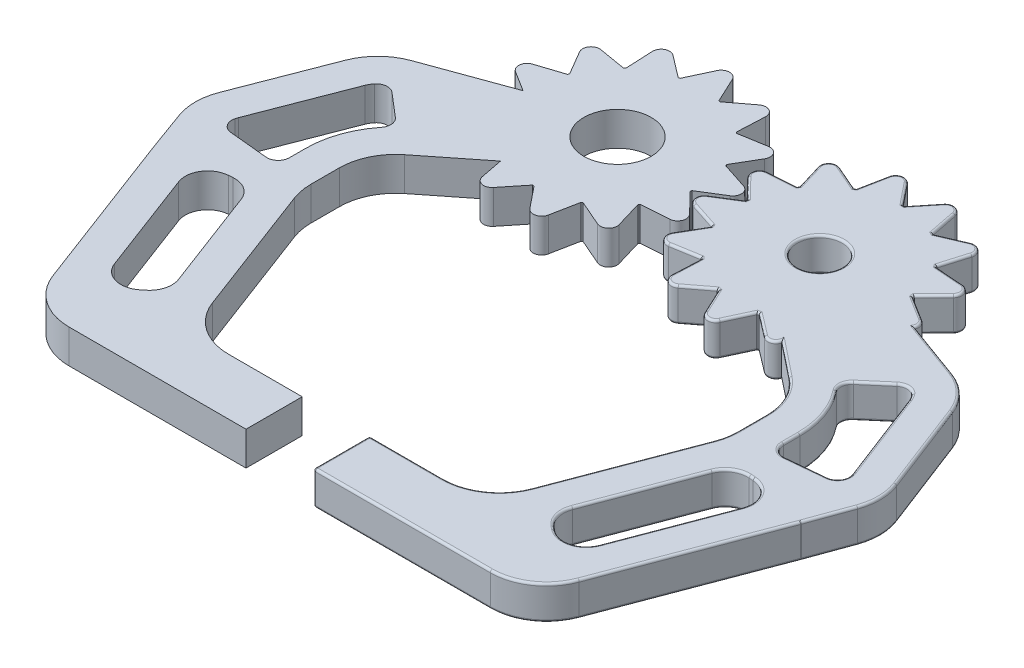
SolidWorks part; units mm, degrees
ref_plane "Front Plane" through (0, 0, 0) normal (0, 0, 1) x (1, 0, 0)
ref_plane "Top Plane" through (0, 0, 0) normal (0, 1, 0) x (1, 0, 0)
ref_plane "Right Plane" through (0, 0, 0) normal (1, 0, 0) x (0, 0, -1)
sketch "Sketch1" plane through (0, 0, 0) normal (0, 1, 0) x (1, 0, 0)
  line L0 (-9, 0) -> (-9, 13.9015) construction
  line L1 (-8.3203, 9.5423) -> (-7.2741, 7.2987)
  line L2 (-9.6797, 9.5423) -> (-10.7259, 7.2987)
  line L3 (-3.9636, 8.1334) -> (-4.0799, 5.6606)
  line L4 (-5.1673, 8.7652) -> (-7.1364, 7.2648)
  line L5 (-0.7607, 4.8612) -> (-2.0128, 2.7257)
  line L6 (-1.533, 5.9801) -> (-3.9737, 5.5666)
  line L7 (0.5547, 0.4754) -> (-1.5465, -0.8336)
  line L8 (0.3908, 1.825) -> (-1.9625, 2.5931)
  line L9 (-0.3188, -4.0193) -> (-2.7876, -4.2019)
  line L10 (0.1633, -2.7482) -> (-1.5636, -0.9744)
  line L11 (-3.1811, -7.5933) -> (-5.4519, -6.6077)
  line L12 (-2.1635, -6.6918) -> (-2.8682, -4.3187)
  line L13 (-7.3764, -9.4277) -> (-8.9291, -7.4997)
  line L14 (-6.0564, -9.1024) -> (-5.5775, -6.6736)
  line L15 (-11.9436, -9.1024) -> (-12.4225, -6.6736)
  line L16 (-10.6236, -9.4277) -> (-9.0709, -7.4997)
  line L17 (-15.8365, -6.6918) -> (-15.1318, -4.3187)
  line L18 (-14.8189, -7.5933) -> (-12.5481, -6.6077)
  line L19 (-18.1633, -2.7482) -> (-16.4364, -0.9744)
  line L20 (-17.6812, -4.0193) -> (-15.2124, -4.2019)
  line L21 (-18.3908, 1.825) -> (-16.0375, 2.5931)
  line L22 (-18.5547, 0.4754) -> (-16.4535, -0.8336)
  line L23 (-16.467, 5.9801) -> (-14.0263, 5.5666)
  line L24 (-17.2393, 4.8612) -> (-15.9872, 2.7257)
  line L25 (-12.8327, 8.7652) -> (-10.8636, 7.2648)
  line L26 (-14.0364, 8.1334) -> (-13.9201, 5.6606)
  circle A0 centre (-9, 0) radius 10 construction
  circle A1 centre (9, 0) radius 10 construction
  arc A2 (-7.1364, 7.2648) -> (-7.2741, 7.2987) centre (-9, 0) ccw
  arc A3 (-8.3203, 9.5423) -> (-9.6797, 9.5423) centre (-9, 9.2253) ccw
  arc A4 (-3.9636, 8.1334) -> (-5.1673, 8.7652) centre (-4.7128, 8.1686) ccw
  arc A5 (-0.7607, 4.8612) -> (-1.533, 5.9801) centre (-1.4077, 5.2406) ccw
  arc A6 (0.5547, 0.4754) -> (0.3908, 1.825) centre (0.1581, 1.112) ccw
  arc A7 (-0.3188, -4.0193) -> (0.1633, -2.7482) centre (-0.3741, -3.2714) ccw
  arc A8 (-3.1811, -7.5933) -> (-2.1635, -6.6918) centre (-2.8825, -6.9053) ccw
  arc A9 (-7.3764, -9.4277) -> (-6.0564, -9.1024) centre (-6.7922, -8.9573) ccw
  arc A10 (-11.9436, -9.1024) -> (-10.6236, -9.4277) centre (-11.2078, -8.9573) ccw
  arc A11 (-15.8365, -6.6918) -> (-14.8189, -7.5933) centre (-15.1175, -6.9053) ccw
  arc A12 (-18.1633, -2.7482) -> (-17.6812, -4.0193) centre (-17.6259, -3.2714) ccw
  arc A13 (-18.3908, 1.825) -> (-18.5547, 0.4754) centre (-18.1581, 1.112) ccw
  arc A14 (-16.467, 5.9801) -> (-17.2393, 4.8612) centre (-16.5923, 5.2406) ccw
  arc A15 (-12.8327, 8.7652) -> (-14.0364, 8.1334) centre (-13.2872, 8.1686) ccw
  arc A16 (-10.7259, 7.2987) -> (-10.8636, 7.2648) centre (-9, 0) ccw
  arc A17 (-13.9201, 5.6606) -> (-14.0263, 5.5666) centre (-9, 0) ccw
  arc A18 (-15.9872, 2.7257) -> (-16.0375, 2.5931) centre (-9, 0) ccw
  arc A19 (-16.4535, -0.8336) -> (-16.4364, -0.9744) centre (-9, 0) ccw
  arc A20 (-15.2124, -4.2019) -> (-15.1318, -4.3187) centre (-9, 0) ccw
  arc A21 (-12.5481, -6.6077) -> (-12.4225, -6.6736) centre (-9, 0) ccw
  arc A22 (-9.0709, -7.4997) -> (-8.9291, -7.4997) centre (-9, 0) ccw
  arc A23 (-5.5775, -6.6736) -> (-5.4519, -6.6077) centre (-9, 0) ccw
  arc A24 (-2.8682, -4.3187) -> (-2.7876, -4.2019) centre (-9, 0) ccw
  arc A25 (-1.5636, -0.9744) -> (-1.5465, -0.8336) centre (-9, 0) ccw
  arc A26 (-1.9625, 2.5931) -> (-2.0128, 2.7257) centre (-9, 0) ccw
  arc A27 (-3.9737, 5.5666) -> (-4.0799, 5.6606) centre (-9, 0) ccw
  point P15 (-9, 11)
  point P75 (-9, 0)
  dimension "D1" = 20
  dimension "D2" = 20
  dimension "D5" = 15
  dimension "D8" = 0.75
  dimension "D3" = 18
  dimension "D4" = 9
  dimension "D6" = 25
  dimension "D7" = 11
  dimension "D9" = 13
extrude "Boss-Extrude1" add sketch "Sketch1" along normal blind 3
sketch "Sketch2" plane through (0, 0, 0) normal (0, 1, 0) x (1, 0, 0)
  line L0 (9, 0) -> (12.5984, 14.6004) construction
  line L1 (11.9434, 9.1024) -> (12.4223, 6.6736)
  line L2 (10.6235, 9.4277) -> (9.0708, 7.4997)
  line L3 (15.8364, 6.6919) -> (15.1317, 4.3188)
  line L4 (14.8188, 7.5934) -> (12.5479, 6.6077)
  line L5 (18.1632, 2.7484) -> (16.4364, 0.9745)
  line L6 (17.6811, 4.0195) -> (15.2123, 4.2021)
  line L7 (18.3908, -1.8248) -> (16.0375, -2.593)
  line L8 (18.5547, -0.4752) -> (16.4535, 0.8337)
  line L9 (16.4672, -5.9799) -> (14.0264, -5.5665)
  line L10 (17.2394, -4.8611) -> (15.9872, -2.7256)
  line L11 (12.8328, -8.7651) -> (10.8638, -7.2647)
  line L12 (14.0366, -8.1333) -> (13.9202, -5.6605)
  line L13 (8.3205, -9.5423) -> (7.2742, -7.2987)
  line L14 (9.6799, -9.5423) -> (10.7261, -7.2987)
  line L15 (3.9638, -8.1335) -> (4.08, -5.6607)
  line L16 (5.1675, -8.7653) -> (7.1365, -7.2648)
  line L17 (0.7608, -4.8614) -> (2.0129, -2.7259)
  line L18 (1.5331, -5.9802) -> (3.9738, -5.5667)
  line L19 (-0.5547, -0.4756) -> (1.5465, 0.8334)
  line L20 (-0.3908, -1.8252) -> (1.9626, -2.5933)
  line L21 (0.3187, 4.0191) -> (2.7875, 4.2018)
  line L22 (-0.1633, 2.748) -> (1.5635, 0.9742)
  line L23 (3.1809, 7.5932) -> (5.4518, 6.6076)
  line L24 (2.1634, 6.6916) -> (2.8681, 4.3185)
  line L25 (7.3762, 9.4277) -> (8.9289, 7.4997)
  line L26 (6.0562, 9.1023) -> (5.5774, 6.6735)
  line L27 (9, 0) -> (9, 20.9978) construction
  arc A0 (5.5774, 6.6735) -> (5.4518, 6.6076) centre (9, 0) ccw
  arc A1 (11.9434, 9.1024) -> (10.6235, 9.4277) centre (11.2076, 8.9573) ccw
  arc A2 (15.8364, 6.6919) -> (14.8188, 7.5934) centre (15.1174, 6.9054) ccw
  arc A3 (18.1632, 2.7484) -> (17.6811, 4.0195) centre (17.6258, 3.2715) ccw
  arc A4 (18.3908, -1.8248) -> (18.5547, -0.4752) centre (18.1581, -1.1118) ccw
  arc A5 (16.4672, -5.9799) -> (17.2394, -4.8611) centre (16.5924, -5.2404) ccw
  arc A6 (12.8328, -8.7651) -> (14.0366, -8.1333) centre (13.2874, -8.1686) ccw
  arc A7 (8.3205, -9.5423) -> (9.6799, -9.5423) centre (9.0002, -9.2253) ccw
  arc A8 (3.9638, -8.1335) -> (5.1675, -8.7653) centre (4.7129, -8.1687) ccw
  arc A9 (0.7608, -4.8614) -> (1.5331, -5.9802) centre (1.4078, -5.2407) ccw
  arc A10 (-0.5547, -0.4756) -> (-0.3908, -1.8252) centre (-0.1581, -1.1122) ccw
  arc A11 (0.3187, 4.0191) -> (-0.1633, 2.748) centre (0.3741, 3.2712) ccw
  arc A12 (3.1809, 7.5932) -> (2.1634, 6.6916) centre (2.8823, 6.9051) ccw
  arc A13 (7.3762, 9.4277) -> (6.0562, 9.1023) centre (6.792, 8.9572) ccw
  arc A14 (2.8681, 4.3185) -> (2.7875, 4.2018) centre (9, 0) ccw
  arc A15 (1.5635, 0.9742) -> (1.5465, 0.8334) centre (9, 0) ccw
  arc A16 (1.9626, -2.5933) -> (2.0129, -2.7259) centre (9, 0) ccw
  arc A17 (3.9738, -5.5667) -> (4.08, -5.6607) centre (9, 0) ccw
  arc A18 (7.1365, -7.2648) -> (7.2742, -7.2987) centre (9, 0) ccw
  arc A19 (10.7261, -7.2987) -> (10.8638, -7.2647) centre (9, 0) ccw
  arc A20 (13.9202, -5.6605) -> (14.0264, -5.5665) centre (9, 0) ccw
  arc A21 (15.9872, -2.7256) -> (16.0375, -2.593) centre (9, 0) ccw
  arc A22 (16.4535, 0.8337) -> (16.4364, 0.9745) centre (9, 0) ccw
  arc A23 (15.2123, 4.2021) -> (15.1317, 4.3188) centre (9, 0) ccw
  arc A24 (12.5479, 6.6077) -> (12.4223, 6.6736) centre (9, 0) ccw
  arc A25 (9.0708, 7.4997) -> (8.9289, 7.4997) centre (9, 0) ccw
  point P11 (11.6323, 10.6804)
  point P73 (9, 0)
  dimension "D1" = 15
  dimension "D2" = 25
  dimension "D4" = 0.75
  dimension "D3" = 11
  dimension "D6" = 13.845
  dimension "D5" = 13
extrude "Boss-Extrude2" add sketch "Sketch2" along normal blind 3 separate body
sketch "Sketch3" plane through (0, 3, 0) normal (0, 1, 0) x (1, 0, 0)
  circle A0 centre (-9, 0) radius 3
  dimension "D1" = 6
extrude "Cut-Extrude1" cut sketch "Sketch3" against normal blind 3
sketch "Sketch4" plane through (0, 3, 0) normal (0, 1, 0) x (1, 0, 0)
  line L0 (-12, 0) -> (-15, 0)
  line L1 (-15, 0) -> (-24.0634, -3.2988)
  line L2 (-30.1807, -17.8135) -> (-28.8453, -21.4827)
  line L3 (-18.7439, -39.0643) -> (-3, -39.0643)
  line L4 (-12, -5.2004) -> (-11.2334, -6.1968)
  line L5 (-11.2334, -6.1968) -> (-17.0992, -10.8467)
  line L6 (-18.9932, -14.765) -> (-18.9932, -17.308)
  line L7 (-18.6701, -19.0761) -> (-14.2257, -30.8324)
  line L8 (-3, -34.0643) -> (-3, -39.0643)
  line L9 (-12, 0) -> (-12, -5.2004)
  line L10 (-9.5488, -34.0643) -> (-3, -34.0643)
  line L11 (-27.0179, -6.1968) -> (-30.1468, -14.3029)
  line L12 (-23.4209, -35.8324) -> (-28.8237, -21.5407)
  line L13 (0, 0) -> (0, 23.1588) construction
  line L14 (23.4209, -35.8324) -> (28.8237, -21.5407)
  line L15 (27.0179, -6.1968) -> (30.1468, -14.3029)
  line L16 (9.5488, -34.0643) -> (3, -34.0643)
  line L17 (12, 0) -> (12, -5.2004)
  line L18 (3, -34.0643) -> (3, -39.0643)
  line L19 (18.6701, -19.0761) -> (14.2257, -30.8324)
  line L20 (18.9932, -14.765) -> (18.9932, -17.308)
  line L21 (11.2334, -6.1968) -> (17.0992, -10.8467)
  line L22 (12, -5.2004) -> (11.2334, -6.1968)
  line L23 (18.7439, -39.0643) -> (3, -39.0643)
  line L24 (30.1807, -17.8135) -> (28.8453, -21.4827)
  line L25 (15, 0) -> (24.0634, -3.2988)
  line L26 (12, 0) -> (15, 0)
  line L27 (-24.2191, -7.2771) -> (-27.3481, -15.3832)
  line L28 (-21.9932, -14.765) -> (-21.9932, -17.308) construction
  line L29 (-21.9932, -14.765) -> (-21.9932, -16.2063)
  line L30 (-22.4737, -6.6004) -> (-20.3791, -8.3936)
  line L31 (-26.5513, -16.866) -> (-23.0897, -17.2017)
  line L32 (-13.097, -3.8458) -> (-18.9628, -8.4958) construction
  line L33 (-21.5893, -32.1934) -> (-25.0724, -22.9801)
  line L34 (-20.9471, -21.5367) -> (-17.5451, -30.5358)
  line L35 (-23.3522, -20.2786) -> (-22.9685, -20.2496)
  line L36 (-18.1633, -32.8022) -> (-18.466, -33.0453)
  line L37 (-21.4763, -20.1369) -> (-17.0319, -31.8932) construction
  line L38 (-20.6147, -34.7715) -> (-26.0176, -20.4798) construction
  line L39 (21.5893, -32.1934) -> (25.0724, -22.9801)
  line L40 (24.2191, -7.2771) -> (27.3481, -15.3832)
  line L41 (22.4737, -6.6004) -> (20.3791, -8.3936)
  line L42 (23.3522, -20.2786) -> (22.9685, -20.2496)
  line L43 (26.5513, -16.866) -> (23.0897, -17.2017)
  line L44 (21.9932, -14.765) -> (21.9932, -16.2063)
  line L45 (18.1633, -32.8022) -> (18.466, -33.0453)
  line L46 (20.9471, -21.5367) -> (17.5451, -30.5358)
  circle A0 centre (-9, 0) radius 3 construction
  arc A1 (-17.0992, -10.8467) -> (-18.9932, -14.765) centre (-13.9932, -14.765) ccw
  arc A2 (-27.0179, -6.1968) -> (-24.0634, -3.2988) centre (-22.3533, -7.9973) cw
  arc A3 (-14.2257, -30.8324) -> (-9.5488, -34.0643) centre (-9.5488, -29.0643) ccw
  arc A4 (-23.4209, -35.8324) -> (-18.7439, -39.0643) centre (-18.7439, -34.0643) ccw
  arc A5 (-28.8237, -21.5407) -> (-28.8453, -21.4827) centre (-24.1468, -19.7726) cw
  arc A6 (-18.9932, -17.308) -> (-18.6701, -19.0761) centre (-13.9932, -17.308) ccw
  arc A7 (-30.1468, -14.3029) -> (-30.1807, -17.8135) centre (-25.4823, -16.1034) ccw
  arc A8 (30.1468, -14.3029) -> (30.1807, -17.8135) centre (25.4823, -16.1034) cw
  arc A9 (18.9932, -17.308) -> (18.6701, -19.0761) centre (13.9932, -17.308) cw
  arc A10 (28.8237, -21.5407) -> (28.8453, -21.4827) centre (24.1468, -19.7726) ccw
  arc A11 (23.4209, -35.8324) -> (18.7439, -39.0643) centre (18.7439, -34.0643) cw
  arc A12 (14.2257, -30.8324) -> (9.5488, -34.0643) centre (9.5488, -29.0643) cw
  arc A13 (27.0179, -6.1968) -> (24.0634, -3.2988) centre (22.3533, -7.9973) ccw
  arc A14 (17.0992, -10.8467) -> (18.9932, -14.765) centre (13.9932, -14.765) cw
  arc A15 (-24.2191, -7.2771) -> (-23.8947, -6.7229) centre (-22.3533, -7.9973) cw
  arc A16 (-27.3481, -15.3832) -> (-27.4274, -15.638) centre (-25.4823, -16.1034) ccw
  arc A17 (-20.2476, -9.7768) -> (-21.9932, -14.765) centre (-13.9932, -14.765) ccw
  arc A18 (-27.3481, -15.3832) -> (-27.3617, -16.7874) centre (-25.4823, -16.1034) ccw construction
  arc A19 (-18.9628, -8.4958) -> (-21.9932, -14.765) centre (-13.9932, -14.765) ccw construction
  arc A20 (-27.4274, -15.638) -> (-26.5513, -16.866) centre (-26.4548, -15.8707) ccw
  arc A21 (-21.9932, -16.2063) -> (-23.0897, -17.2017) centre (-22.9932, -16.2063) cw
  arc A22 (-20.3791, -8.3936) -> (-20.2476, -9.7768) centre (-21.0294, -9.1533) cw
  arc A23 (-24.2191, -7.2771) -> (-23.0374, -6.1179) centre (-22.3533, -7.9973) cw construction
  arc A24 (-23.8947, -6.7229) -> (-22.4737, -6.6004) centre (-23.124, -7.3601) cw
  arc A25 (-17.5451, -30.5358) -> (-18.1633, -32.8022) centre (-19.4159, -31.243) cw
  arc A26 (-20.9471, -21.5367) -> (-22.9685, -20.2496) centre (-22.8179, -22.2439) ccw
  arc A27 (-25.0724, -22.9801) -> (-23.3522, -20.2786) centre (-23.2016, -22.2729) cw
  arc A28 (-21.5893, -32.1934) -> (-18.466, -33.0453) centre (-19.7186, -31.4862) ccw
  arc A29 (23.8947, -6.7229) -> (22.4737, -6.6004) centre (23.124, -7.3601) ccw
  arc A30 (20.3791, -8.3936) -> (20.2476, -9.7768) centre (21.0294, -9.1533) ccw
  arc A31 (24.2191, -7.2771) -> (23.8947, -6.7229) centre (22.3533, -7.9973) ccw
  arc A32 (25.0724, -22.9801) -> (23.3522, -20.2786) centre (23.2016, -22.2729) ccw
  arc A33 (20.9471, -21.5367) -> (22.9685, -20.2496) centre (22.8179, -22.2439) cw
  arc A34 (21.9932, -16.2063) -> (23.0897, -17.2017) centre (22.9932, -16.2063) ccw
  arc A35 (27.4274, -15.638) -> (26.5513, -16.866) centre (26.4548, -15.8707) cw
  arc A36 (20.2476, -9.7768) -> (21.9932, -14.765) centre (13.9932, -14.765) cw
  arc A37 (21.5893, -32.1934) -> (18.466, -33.0453) centre (19.7186, -31.4862) cw
  arc A38 (17.5451, -30.5358) -> (18.1633, -32.8022) centre (19.4159, -31.243) ccw
  arc A39 (27.3481, -15.3832) -> (27.4274, -15.638) centre (25.4823, -16.1034) cw
  dimension "D6" = 5
  dimension "D7" = 5
  dimension "D10" = 1
  dimension "D13" = 2
  dimension "D1" = 3
  dimension "D2" = 5
  dimension "D3" = 3
  dimension "D4" = 20
  dimension "D5" = 90
  dimension "D8" = 3
  dimension "D9" = 3
  dimension "D11" = 3
  dimension "D12" = 3
extrude "Boss-Extrude3" add sketch "Sketch4" against normal blind 3
sketch "Sketch5" plane through (0, 3, 0) normal (0, 1, 0) x (1, 0, 0)
  circle A0 centre (9, 0) radius 2
  dimension "D1" = 4
extrude "Cut-Extrude2" cut sketch "Sketch5" against normal blind 10
fillet "Fillet1" radius 0.2 166 edges at (3, 1.5, 39.0643) (3, 1.5, 34.0643) (18.3146, 0, 32.9237) (17.4864, 0, 31.7693) (19.2461, 0, 26.0362) (21.7437, 0, 20.5569) (23.1603, 0, 20.2641) (24.8886, 0, 21.1987) (23.3308, 0, 27.5868) (20.2449, 0, 33.4157) (25.7836, 0, 11.3301) (27.392, 0, 15.5093) (27.2689, 0, 16.4514) (24.8205, 0, 17.0338) (22.321, 0, 16.9468) (21.9932, 0, 15.4856) (21.5442, 0, 12.1226) (20.0339, 0, 9.0586) (21.4264, 0, 7.497) (23.2099, 0, 6.3638) (24.0793, 0, 6.9869) (18.4948, 0, 12.589) (18.9932, 0, 16.0365) (18.9117, 0, 18.2067) (16.4479, 0, 24.9542) (12.3913, 0, 33.1777) (6.2744, 0, 34.0643) (3, 0, 36.5643) (10.872, 0, 39.0643) (21.5864, 0, 38.1777) (26.1223, 0, 28.6865) (28.8346, 0, 21.5117) (29.513, 0, 19.6481) (30.482, 0, 16.0551) (28.5824, 0, 10.2498) (25.8545, 0, 4.4278) (21.4567, 0, 2.35) (18.8727, 0, 0.8839) (17.5041, 0, -0.1793) (16.4453, 0, -0.9042) (17.2998, 0, -1.8614) (18.327, 0, -3.5375) (16.4467, 0, -4.1108) (15.1723, 0, -4.2606) (15.4841, 0, -5.5053) (15.6147, 0, -7.4668) (13.6834, 0, -7.1006) (12.4853, 0, -6.641) (12.1829, 0, -7.888) (11.3871, 0, -9.6855) (9.8471, 0, -8.4637) (8.9998, 0, -7.5) (8.1526, 0, -8.4637) (6.6125, 0, -9.6854) (5.8168, 0, -7.8879) (5.5144, 0, -6.6409) (4.3164, 0, -7.1004) (2.385, 0, -7.4665) (2.5157, 0, -5.5051) (2.8275, 0, -4.2604) (1.5531, 0, -4.1105) (-0.3272, 0, -3.5371) (0.7001, 0, -1.8611) (1.5547, 0, -0.9039) (0.4959, 0, -0.1789) (-0.9026, 0, 1.2026) (0.7859, 0, 2.2092) (1.9874, 0, 2.6597) (1.3868, 0, 3.7936) (0.7906, 0, 5.6668) (2.7535, 0, 5.7734) (4.0267, 0, 5.6139) (4.0219, 0, 6.8971) (4.3644, 0, 8.8328) (6.152, 0, 8.015) (7.2053, 0, 7.2821) (7.7973, 0, 8.4205) (9.0002, 0, 9.9753) (10.203, 0, 8.4205) (10.795, 0, 7.282) (11.8483, 0, 8.0149) (13.5149, 0, 8.8832) (15.5512, 0, 9.6196) (9, 0, 2) (24.8886, 3, 21.1987) (23.1603, 3, 20.2641) (21.7437, 3, 20.5569) (19.2461, 3, 26.0362) (17.4864, 3, 31.7693) (18.3146, 3, 32.9237) (20.2449, 3, 33.4157) (23.3308, 3, 27.5868) (21.4264, 3, 7.497) (20.0339, 3, 9.0586) (21.5442, 3, 12.1226) (21.9932, 3, 15.4856) (22.321, 3, 16.9468) (24.8205, 3, 17.0338) (27.2689, 3, 16.4514) (27.392, 3, 15.5093) (25.7836, 3, 11.3301) (24.0793, 3, 6.9869) (23.2099, 3, 6.3638) (11.8483, 3, 8.0149) (10.795, 3, 7.282) (10.203, 3, 8.4205) (9.0002, 3, 9.9753) (7.7973, 3, 8.4205) (7.2053, 3, 7.2821) (6.152, 3, 8.015) (4.3644, 3, 8.8328) (4.0219, 3, 6.8971) (4.0267, 3, 5.6139) (2.7535, 3, 5.7734) (0.7906, 3, 5.6668) (1.3868, 3, 3.7936) (1.9874, 3, 2.6597) (0.7859, 3, 2.2092) (-0.9026, 3, 1.2026) (0.4959, 3, -0.1789) (1.5547, 3, -0.9039) (0.7001, 3, -1.8611) (-0.3272, 3, -3.5371) (1.5531, 3, -4.1105) (2.8275, 3, -4.2604) (2.5157, 3, -5.5051) (2.385, 3, -7.4665) (4.3164, 3, -7.1004) (5.5144, 3, -6.6409) (5.8168, 3, -7.8879) (6.6125, 3, -9.6854) (8.1526, 3, -8.4637) (8.9998, 3, -7.5) (9.8471, 3, -8.4637) (11.3871, 3, -9.6855) (12.1829, 3, -7.888) (12.4853, 3, -6.641) (13.6834, 3, -7.1006) (15.6147, 3, -7.4668) (15.4841, 3, -5.5053) (15.1723, 3, -4.2606) (16.4467, 3, -4.1108) (18.327, 3, -3.5375) (17.2998, 3, -1.8614) (16.4453, 3, -0.9042) (17.5041, 3, -0.1793) (18.8727, 3, 0.8839) (21.4567, 3, 2.35) (25.8545, 3, 4.4278) (28.5824, 3, 10.2498) (30.482, 3, 16.0551) (29.513, 3, 19.6481) (28.8346, 3, 21.5117) (26.1223, 3, 28.6865) (21.5864, 3, 38.1777) (10.872, 3, 39.0643) (3, 3, 36.5643) (6.2744, 3, 34.0643) (12.3913, 3, 33.1777) (16.4479, 3, 24.9542) (18.9117, 3, 18.2067) (18.9932, 3, 16.0365) (18.4948, 3, 12.589) (15.5512, 3, 9.6196) (13.5149, 3, 8.8832) (9, 3, 2)
